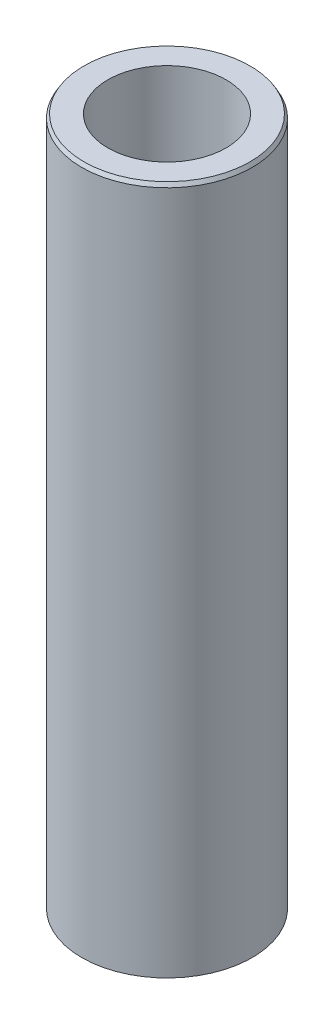
SolidWorks part; units mm, degrees
ref_plane "Front Plane" through (0, 0, 0) normal (0, 0, 1) x (1, 0, 0)
ref_plane "Top Plane" through (0, 0, 0) normal (0, 1, 0) x (1, 0, 0)
ref_plane "Right Plane" through (0, 0, 0) normal (1, 0, 0) x (0, 0, -1)
sketch "Sketch1" plane through (0, 0, 0) normal (0, 1, 0) x (1, 0, 0)
  circle A0 centre (0, 0) radius 52.5
  dimension "SHAFT_OD" = 105
extrude "Boss-Extrude1" add sketch "Sketch1" along normal blind 424.9884
sketch "Sketch2" plane through (0, 0, 0) normal (0, 1, 0) x (1, 0, 0)
  circle A0 centre (0, 0) radius 36.3998
  dimension "BORE_D" = 72.7996
extrude "Cut-Extrude1" cut sketch "Sketch2" along normal through all
chamfer "Chamfer1" distance 2.3249 angle 30 2 edges at (0, 424.9884, 52.5) (0, 0, 52.5) first distance on face at (0, 424.9884, 52.5) first distance on face at (0, 0, 36.3998)
